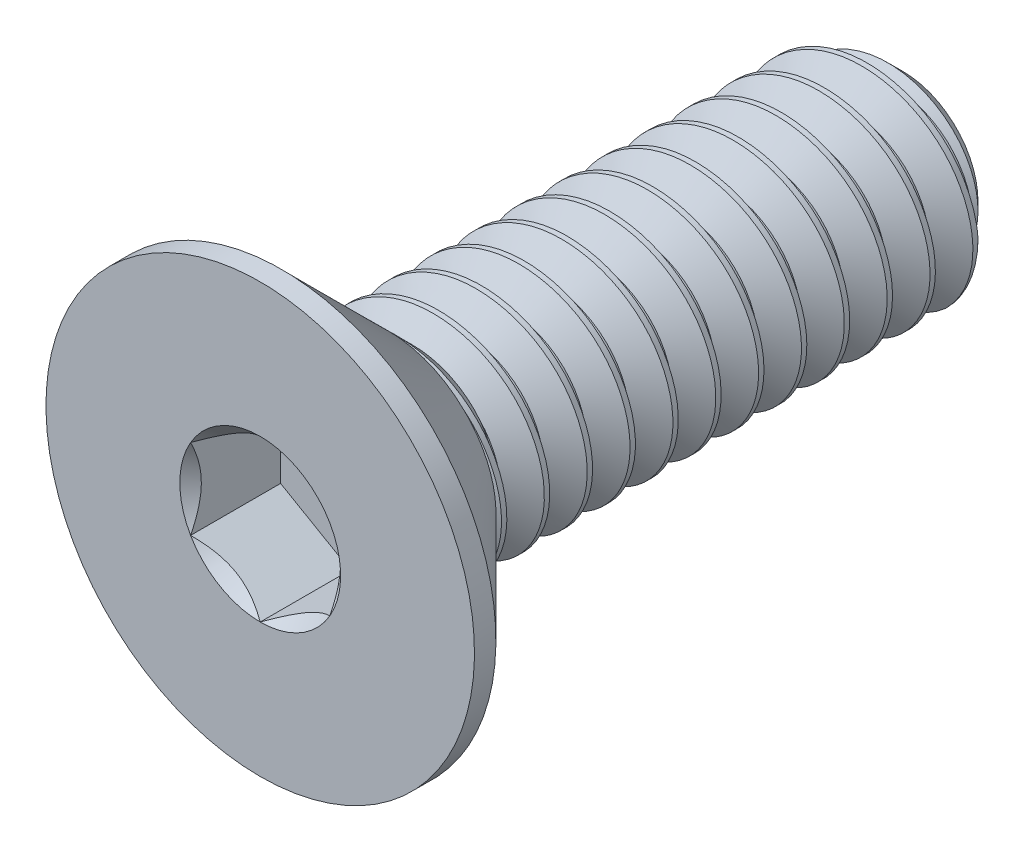
SolidWorks part; units mm, degrees
material "Brass"
ref_plane "Front" through (0, 0, 0) normal (0, 0, 1) x (1, 0, 0)
ref_plane "Top" through (0, 0, 0) normal (0, 1, 0) x (1, 0, 0)
ref_plane "Right" through (0, 0, 0) normal (1, 0, 0) x (0, 0, -1)
sketch "Sketch1" plane through (0, 0, 0) normal (1, 0, 0) x (0, 0, -1)
  line L0 (0, 2) -> (0.2, 2) construction
  line L1 (0.2, 2) -> (1.2, 1) construction
  line L2 (0, 1) -> (6, 1)
  line L3 (6, 1) -> (6, 0)
  line L4 (6, 0) -> (0, 0)
  line L5 (0, 0) -> (0, 2) construction
  line L6 (0, 2) -> (0, -2) construction
  line L7 (6, 1) -> (6, -1) construction
  line L8 (0, -2) -> (0.2, -2) construction
  line L9 (0.2, -2) -> (1.2, -1) construction
  line L11 (0, 1) -> (0, 0)
  line L12 (1.2, 1) -> (1.2, 0) construction
revolve "Revolve1" add sketch "Sketch1" angle 360 mid plane about L4
sketch "Sketch3" plane through (0, 0, -6) normal (0, 0, -1) x (-1, 0, 0)
  circle A0 centre (0, 0) radius 1
curve "Helix/Spiral1" pitch 0.4 height 6 radius 1 centre (0, 0, -6) axis (0, 0, 1) start towards (0, 1, 0)
sketch "Sketch2" plane through (0, 0, 0) normal (1, 0, 0) x (0, 0, -1)
  line L0 (6, 1) -> (6.35, 1)
  line L1 (6.35, 1) -> (6.2, 0.7402)
  line L2 (6.2, 0.7402) -> (6.15, 0.7402)
  line L3 (6.15, 0.7402) -> (6, 1)
  line L4 (6.075, 0.8701) -> (6.275, 0.8701) construction
  dimension "D1" = 60
  dimension "D2" = 0.05
  dimension "D3" = 0.2
chamfer "Chamfer1" distance 0.3 angle 45 1 edges at (0, 1, -6)
sweep "Cut-Sweep1" cut profiles "Sketch2" path "Helix/Spiral1" align with end faces yes
sketch "Sketch7" plane through (0, 0, 0) normal (1, 0, 0) x (0, 0, -1)
  line L0 (0, 2) -> (0.2, 2) construction
  line L1 (0.2, 2) -> (1.2, 1) construction
  line L2 (0, 2) -> (0.2, 2)
  line L3 (0.2, 2) -> (1.2, 1)
  line L4 (1.2, 1) -> (1.2, 0) construction
  line L5 (1.2, 1) -> (1.2, 0)
  line L7 (0, 0) -> (0, 2) construction
  line L8 (0, 0) -> (0, 2)
  line L9 (0, 0) -> (1.2, 0)
  line L10 (3.85, 0) -> (-3.85, 0) construction
revolve "Revolve2" add sketch "Sketch7" angle 360 mid plane about L9
ref_plane "Plane1" through (0, 0, -1.2) normal (0, 0, 1) x (1, 0, 0)
sketch "Sketch8" plane through (0, 0, -1.2) normal (0, 0, 1) x (1, 0, 0)
  circle A0 centre (0, 0) radius 1
extrude "Boss-Extrude1" add sketch "Sketch8" against normal through all draft 45
sketch "Sketch5" plane through (0, 0, 0) normal (0, 0, 1) x (1, 0, 0)
  line L1 (0.65, -0.3753) -> (0.65, 0.3753)
  line L2 (0.65, 0.3753) -> (0, 0.7506)
  line L3 (0, 0.7506) -> (-0.65, 0.3753)
  line L4 (-0.65, 0.3753) -> (-0.65, -0.3753)
  line L5 (-0.65, -0.3753) -> (0, -0.7506)
  line L6 (0, -0.7506) -> (0.65, -0.3753)
  circle A0 centre (0, 0) radius 0.65 construction
  dimension "Hex" = 1.3
extrude "Cut-Extrude2" cut sketch "Sketch5" against normal blind 0.84
sketch "Sketch6" plane through (0, 0, 0) normal (0, 0, 1) x (1, 0, 0)
  circle A0 centre (0, 0) radius 0.7506
extrude "Cut-Extrude3" cut sketch "Sketch6" against normal blind 0.84 draft 45
sketch "Sketch9" [suppressed] plane through (0, 0, -5.5) normal (0, 0, 1) x (1, 0, 0)
  circle A1 centre (0, 0) radius 5
  circle A2 centre (0, 0) radius 5
  point P0 (0, 5)
  dimension "D1" = 0
extrude "Boss-Extrude2" [suppressed] add sketch "Sketch9" against normal offset from surface (18.5 mm away) 26 up to face at (0, 0.7, -6)
fillet "Fillet1" [suppressed] radius 0.2
sketch "Sketch10" plane through (0, 0, 0) normal (1, 0, 0) x (0, 0, -1)
  line L0 (6, 1) -> (6, -1) construction
  point P0 (5.4, -1)
  dimension "D1" = 0.6
equation "\"D3@Helix/Spiral1\" = \"Lg@Sketch1\""
equation "\"D2@Sketch2\" = \"D4@Helix/Spiral1\" * .125"
equation "\"D3@Sketch2\" = \"D4@Helix/Spiral1\" * .5"
equation "\"D1@Chamfer1\" = \"D4@Helix/Spiral1\" * .75"
equation "\"D1@Cut-Extrude2\" = \"Head Ht@Sketch1\" * .7"
equation "\"D1@Sketch10\" = \"D4@Helix/Spiral1\" * 1.5"
equation "\"D1@Cut-Extrude3\" = \"D1@Cut-Extrude2\""
equation "\"D1@Fillet1\" = \"Dia@Sketch1\" * .1"
